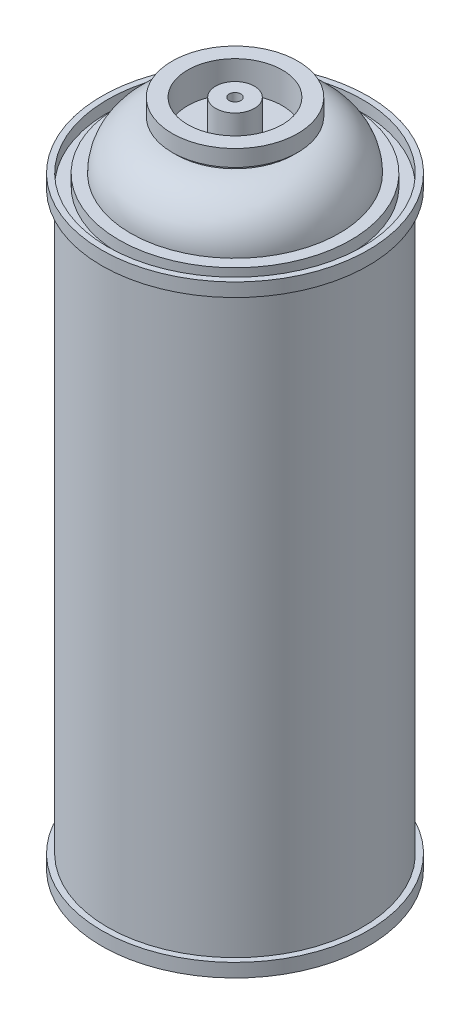
SolidWorks part; units mm, degrees
ref_plane "Front" through (0, 0, 0) normal (0, 0, 1) x (1, 0, 0)
ref_plane "Top" through (0, 0, 0) normal (0, 1, 0) x (1, 0, 0)
ref_plane "Right" through (0, 0, 0) normal (1, 0, 0) x (0, 0, -1)
sketch "Sketch1" plane through (0, 0, 0) normal (0, 1, 0) x (1, 0, 0)
  circle A0 centre (0, 0) radius 33
  dimension "D1" = 66
extrude "Boss-Extrude1" add sketch "Sketch1" along normal blind 156
sketch "Sketch2" plane through (0, 0, 0) normal (1, 0, 0) x (0, 0, -1)
  line L0 (33, 156) -> (27, 156) construction
  line L1 (33, 156) -> (-33, 156) construction
  line L2 (15.25, 167.75) -> (15.25, 168.75)
  line L3 (15.25, 168.75) -> (16.25, 168.75)
  line L4 (16.25, 168.75) -> (16.25, 173)
  line L5 (16.25, 173) -> (12.25, 173)
  line L6 (12.25, 173) -> (12.25, 165)
  line L7 (12.25, 165) -> (5, 165)
  line L8 (5, 165) -> (5, 173)
  line L9 (5, 173) -> (0, 173)
  line L10 (0, 173) -> (0, 156)
  line L11 (27, 156) -> (0, 156)
  arc A0 (27, 156) -> (15.25, 167.75) centre (15.25, 156) ccw
  dimension "D1" = 17
  dimension "D2" = 6
  dimension "D3" = 16.25
  dimension "D4" = 4
  dimension "D5" = 5
  dimension "D6" = 8
  dimension "D7" = 1
revolve "Revolve1" add sketch "Sketch2" angle 360 about L10
sketch "Sketch3" plane through (0, 156, 0) normal (0, 1, 0) x (1, 0, 0)
  circle A0 centre (0, 0) radius 34.5
  dimension "D1" = 69
extrude "Boss-Extrude2" add sketch "Sketch3" against normal blind 3.5
pattern_linear "LPattern1" count 2 spacing 152.5 along (0, -1, 0) of "Boss-Extrude2"
sketch "Sketch5" plane through (0, 0, 0) normal (0, 0, 1) x (1, 0, 0)
  line L0 (0, 0) -> (-32.5, 0)
  line L1 (-34.5, 0) -> (34.5, 0) construction
  line L2 (0, 12) -> (0, 0)
  arc A0 (-32.5, 0) -> (0, 12) centre (0, -38.0104) cw
  point P0 (0, 0)
  dimension "D1" = 12
  dimension "D2" = 2
revolve "Cut-Revolve1" cut sketch "Sketch5" angle 360 about L2
sketch "Sketch6" plane through (0, 173, 0) normal (0, 1, 0) x (1, 0, 0)
  circle A0 centre (0, 0) radius 1.5
  dimension "D1" = 3
extrude "Cut-Extrude1" cut sketch "Sketch6" against normal blind 3.5
sketch "Sketch7" plane through (0, 156, 0) normal (0, 1, 0) x (1, 0, 0)
  circle A0 centre (0, 0) radius 33
  circle A1 centre (0, 0) radius 30
  circle A2 centre (0, 0) radius 34.5 construction
  dimension "D1" = 1.5
  dimension "D2" = 3
extrude "Cut-Extrude2" cut sketch "Sketch7" against normal blind 3
